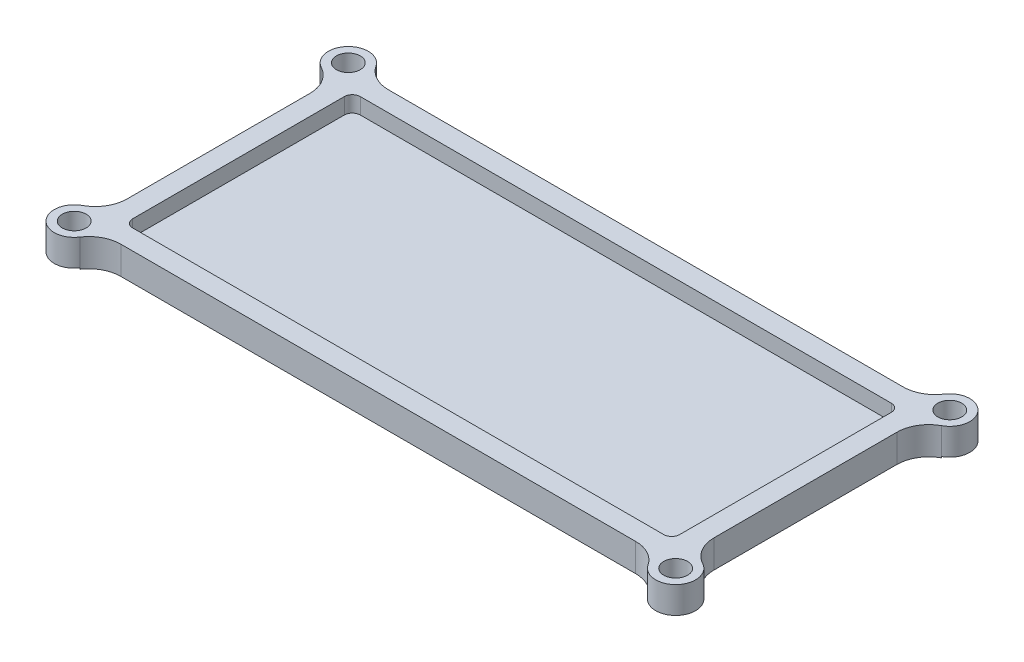
SolidWorks part; units mm, degrees
ref_plane "Front Plane" through (0, 0, 0) normal (0, 0, 1) x (1, 0, 0)
ref_plane "Top Plane" through (0, 0, 0) normal (0, 1, 0) x (1, 0, 0)
ref_plane "Right Plane" through (0, 0, 0) normal (1, 0, 0) x (0, 0, -1)
sketch "Sketch1" plane through (0, 0, 0) normal (0, 1, 0) x (1, 0, 0)
  line L0 (-35.25, 15.25) -> (-36.75, 15.25) construction
  line L1 (35.25, 15.25) -> (-35.25, 15.25)
  line L2 (35.25, 15.25) -> (35.25, -15.25)
  line L3 (35.25, -15.25) -> (-35.25, -15.25)
  line L4 (-35.25, 15.25) -> (-35.25, -15.25)
  line L5 (35.25, 15.25) -> (-35.25, -15.25) construction
  line L6 (35.25, -15.25) -> (-35.25, 15.25) construction
  line L7 (36.75, 16.75) -> (-36.75, 16.75)
  line L8 (36.75, 16.75) -> (36.75, -16.75)
  line L9 (36.75, -16.75) -> (-36.75, -16.75)
  line L10 (-36.75, 16.75) -> (-36.75, -16.75)
  line L11 (36.75, 16.75) -> (-36.75, -16.75) construction
  line L12 (36.75, -16.75) -> (-36.75, 16.75) construction
  line L13 (-35.25, 15.25) -> (-35.25, 16.75) construction
  line L14 (0, 16.75) -> (0, -16.75) construction
  line L15 (-36.75, 0) -> (36.5, 0) construction
  line L16 (-38.6599, 17.1647) -> (-40.1599, 17.1647) construction
  circle A0 centre (-37.6599, 17.1647) radius 1
  circle A1 centre (-37.6599, 17.1647) radius 2.5
  circle A2 centre (37.6599, 17.1647) radius 2.5
  circle A3 centre (37.6599, 17.1647) radius 1
  circle A4 centre (37.6599, -17.1647) radius 1
  circle A5 centre (37.6599, -17.1647) radius 2.5
  circle A6 centre (-37.6599, -17.1647) radius 2.5
  circle A7 centre (-37.6599, -17.1647) radius 1
  point P0 (0, 0)
  point P6 (0, 0)
  dimension "D4" = 2
  dimension "D1" = 30.5
  dimension "D2" = 70.5
  dimension "D3" = 1.5
extrude "Boss-Extrude1" add sketch "Sketch1" along normal blind 1.5 contours L1 L4 L3 L2 | L10 A6 L9 A5 L8 A2 L7 A1 L4 L1 L2 L3 | L10 A1 L7 | L7 A1 L10 A0 | L9 A7 L10 A6 | A6 L10 L9 | L8 A5 L9 | L9 A5 L8 A4 | A2 L8 L7 | L7 A3 L8 A2 region at (0, 0, 0) region at (36.1352, 0, -16.0049) region at (35.9723, 0, -16.8207) region at (35.6572, 0, -15.537) region at (-36.1352, 0, -16.0049) region at (-35.9723, 0, -16.8207) region at (39.0299, 0, 15.1586) region at (36.1352, 0, 16.0049) region at (-36.1352, 0, 16.0049) region at (-36.8207, 0, 15.7931)
sketch "Sketch2" plane through (0, 1.5, 0) normal (0, 1, 0) x (1, 0, 0)
  line L0 (34.25, -14.25) -> (34.25, 14.25)
  line L1 (34.25, 14.25) -> (-34.25, 14.25)
  line L2 (-34.25, 14.25) -> (-34.25, -14.25)
  line L3 (-34.25, -14.25) -> (34.25, -14.25)
  line L4 (36.75, -14.8362) -> (36.75, 14.8362)
  line L5 (35.1946, 16.75) -> (-35.1946, 16.75)
  line L6 (-36.75, 14.8362) -> (-36.75, -14.8362)
  line L7 (-35.1946, -16.75) -> (35.1946, -16.75)
  line L8 (36.75, -14.8362) -> (36.75, 14.8362)
  line L9 (35.1946, 16.75) -> (-35.1946, 16.75)
  line L10 (-36.75, 14.8362) -> (-36.75, -14.8362)
  line L11 (-35.1946, -16.75) -> (35.1946, -16.75)
  arc A0 (34.25, 14.25) -> (34.25, 14.25) centre (34.25, 14.25) ccw
  arc A1 (-34.25, 14.25) -> (-34.25, 14.25) centre (-34.25, 14.25) ccw
  arc A2 (-34.25, -14.25) -> (-34.25, -14.25) centre (-34.25, -14.25) ccw
  arc A3 (34.25, -14.25) -> (34.25, -14.25) centre (34.25, -14.25) ccw
  arc A4 (36.75, 14.8362) -> (35.1946, 16.75) centre (37.6599, 17.1647) ccw
  arc A5 (-35.1946, 16.75) -> (-36.75, 14.8362) centre (-37.6599, 17.1647) ccw
  arc A6 (-36.75, -14.8362) -> (-35.1946, -16.75) centre (-37.6599, -17.1647) ccw
  arc A7 (35.1946, -16.75) -> (36.75, -14.8362) centre (37.6599, -17.1647) ccw
  arc A8 (36.75, 14.8362) -> (35.1946, 16.75) centre (37.6599, 17.1647) ccw
  arc A9 (-35.1946, 16.75) -> (-36.75, 14.8362) centre (-37.6599, 17.1647) ccw
  arc A10 (-36.75, -14.8362) -> (-35.1946, -16.75) centre (-37.6599, -17.1647) ccw
  arc A11 (35.1946, -16.75) -> (36.75, -14.8362) centre (37.6599, -17.1647) ccw
  circle A12 centre (37.6599, -17.1647) radius 1 construction
  circle A13 centre (37.6599, 17.1647) radius 1 construction
  circle A14 centre (-37.6599, 17.1647) radius 1 construction
  circle A15 centre (-37.6599, -17.1647) radius 1 construction
  circle A16 centre (37.6599, -17.1647) radius 1
  circle A17 centre (37.6599, 17.1647) radius 1
  circle A18 centre (-37.6599, 17.1647) radius 1
  circle A19 centre (-37.6599, -17.1647) radius 1
  dimension "D1" = 0
  dimension "D2" = 2.5
extrude "Boss-Extrude2" add sketch "Sketch2" along normal blind 2
fillet "Fillet1" radius 4 8 edges at (36.75, 1.75, -14.8362) (-35.1946, 1.75, -16.75) (36.75, 1.75, 14.8362) (-36.75, 1.75, -14.8362) (35.1946, 1.75, -16.75) (-36.75, 1.75, 14.8362) (35.1946, 1.75, 16.75) (-35.1946, 1.75, 16.75)
hole_wizard "CSK for M2.5 Flat Head Machine Screw1" positions "Sketch5" profile "Sketch6" countersink size "M2.5" standard "ANSI Metric" end condition through all
sketch "Sketch5" plane through (0, 0, 0) normal (0, -1, 0) x (-1, 0, 0)
  point P0 (37.6599, -17.1647)
  point P3 (37.6599, 17.1647)
  point P6 (-37.6599, -17.1647)
  point P9 (-37.6599, 17.1647)
sketch "Sketch6" plane through (-37.6599, 0, 17.1647) normal (1, 0, 0) x (0, 0, -1)
  line L0 (0, 0) -> (0, 3.5)
  line L1 (0, 3.5) -> (1.5, 3.5)
  line L2 (1.5, 3.5) -> (1.5, 1.15)
  line L3 (1.5, 1.15) -> (2.5, 0.15)
  line L4 (2.5, 0.15) -> (2.5, 0)
  line L6 (2.5, 0) -> (0, 0)
  line L7 (-1.5, 1.15) -> (-2.5, 0.15) construction
  line L11 (0, -6.35) -> (0, 107.95) construction
  dimension "Thru Hole Dia." = 3
  dimension "Thru Hole Depth" = 3.5
  dimension "C'Sink Dia." = 5
  dimension "C'Sink Angle" = 90
  dimension "Head Clearance" = 0.15
fillet "Fillet2" radius 1 4 edges at (-34.25, 2.5, 14.25) (34.25, 2.5, 14.25) (-34.25, 2.5, -14.25) (34.25, 2.5, -14.25)
